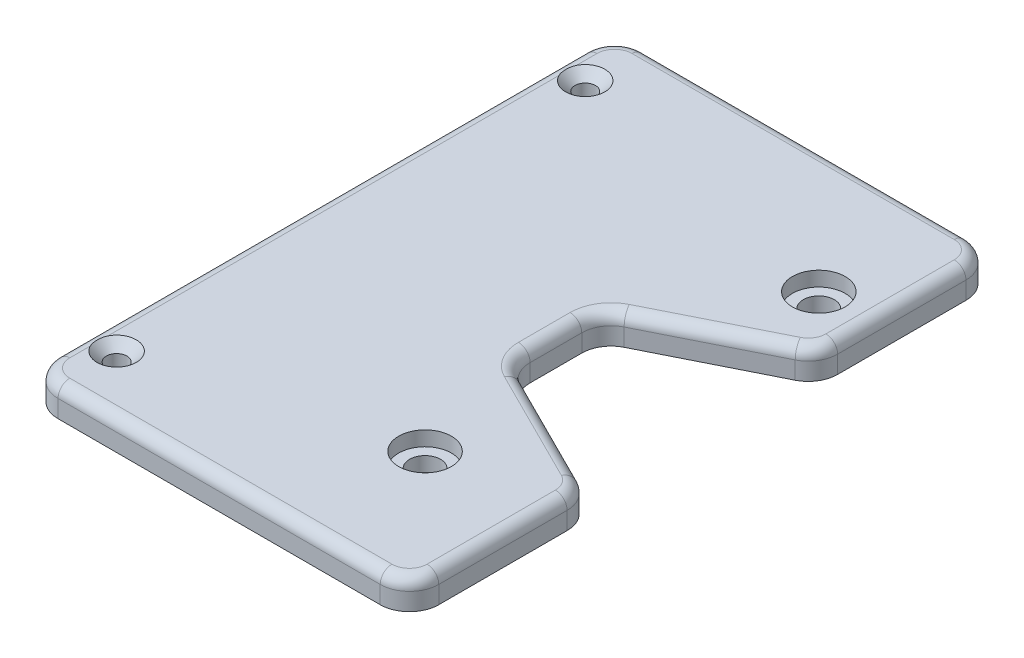
SolidWorks part; units mm, degrees
ref_plane "Front Plane" through (0, 0, 0) normal (0, 0, 1) x (1, 0, 0)
ref_plane "Top Plane" through (0, 0, 0) normal (0, 1, 0) x (1, 0, 0)
ref_plane "Right Plane" through (0, 0, 0) normal (1, 0, 0) x (0, 0, -1)
sketch "Sketch2" plane through (0, 0, 0) normal (0, 1, 0) x (1, 0, 0)
  line L1 (-32.5, 50) -> (32.5, 50)
  line L2 (-32.5, 50) -> (-32.5, -50)
  line L3 (-32.5, -50) -> (32.5, -50)
  line L4 (32.5, 50) -> (32.5, -50)
  line L5 (-32.5, 50) -> (32.5, -50) construction
  line L6 (-32.5, -50) -> (32.5, 50) construction
  circle A0 centre (-27.5, 40) radius 1.75
  circle A1 centre (-27.5, -40) radius 1.75
  circle A2 centre (23.6525, 28.725) radius 2.65
  circle A3 centre (13.65, -28.4925) radius 2.65
  circle A4 centre (23.6525, 28.725) radius 2.5 construction
  circle A5 centre (13.65, -28.4925) radius 2.5 construction
  point P0 (0, 0)
  dimension "D3" = 3.5
  dimension "D4" = 5
  dimension "D8" = 5.3
  dimension "D9" = 5.3
  dimension "D1" = 65
  dimension "D2" = 100
  dimension "D5" = 5
  dimension "D6" = 10
  dimension "D7" = 10
extrude "Boss-Extrude1" add sketch "Sketch2" along normal blind 5
sketch "Sketch3" plane through (0, 5, 0) normal (0, 1, 0) x (1, 0, 0)
  circle A0 centre (23.6525, 28.725) radius 4.5
  circle A1 centre (13.65, -28.4925) radius 4.5
  dimension "D1" = 9
  dimension "D2" = 9
extrude "Cut-Extrude1" cut sketch "Sketch3" against normal blind 2.5
fillet "Fillet1" radius 5 4 edges at (32.5, 2.5, 50) (-32.5, 2.5, -50) (32.5, 2.5, -50) (-32.5, 2.5, 50)
chamfer "Chamfer1" distance 1.6 angle 45 2 edges at (-27.5, 5, 41.75) (-27.5, 5, -38.25)
sketch "Sketch4" plane through (0, 5, 0) normal (0, 1, 0) x (1, 0, 0)
  line L5 (7.5, 7.5) -> (7.5, -7.5)
  line L6 (7.5, -7.5) -> (32.5, -20)
  line L7 (32.5, -45) -> (32.5, 45) construction
  line L8 (32.5, -20) -> (32.5, 20)
  line L9 (32.5, 20) -> (7.5, 7.5)
  point P6 (7.5, 0)
  point P7 (32.5, 0)
  dimension "D1" = 40
  dimension "D2" = 25
  dimension "D3" = 15
extrude "Cut-Extrude2" cut sketch "Sketch4" against normal through all
fillet "Fillet3" radius 5 4 edges at (32.5, 2.5, -20) (32.5, 2.5, 20) (7.5, 2.5, 7.5) (7.5, 2.5, -7.5)
fillet "Fillet2" radius 2 16 edges at (-31.0355, 5, 48.5355) (-32.5, 5, 0) (-31.0355, 5, -48.5355) (0, 5, -50) (31.0355, 5, -48.5355) (32.5, 5, -34.0451) (32.5, 5, 34.0451) (31.0355, 5, 48.5355) (0, 5, 50) (7.5, 5, 0) (31.7533, 5, -20.4615) (20, 5, -13.75) (8.2467, 5, -7.0385) (8.2467, 5, 7.0385) (20, 5, 13.75) (31.7533, 5, 20.4615)
